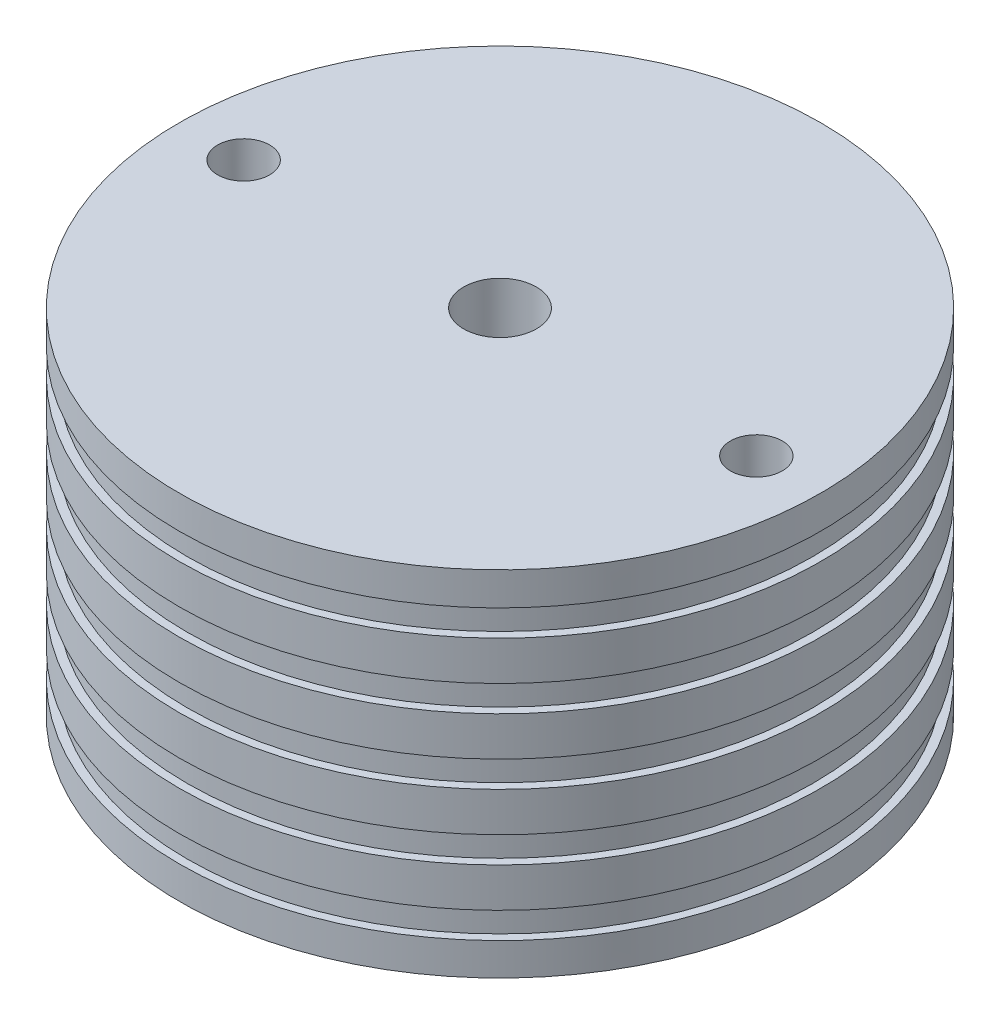
SolidWorks part; units mm, degrees
ref_plane "Front Plane" through (0, 0, 0) normal (0, 0, 1) x (1, 0, 0)
ref_plane "Top Plane" through (0, 0, 0) normal (0, 1, 0) x (1, 0, 0)
ref_plane "Right Plane" through (0, 0, 0) normal (1, 0, 0) x (0, 0, -1)
sketch "Sketch1" plane through (0, 0, 0) normal (0, 0, 1) x (1, 0, 0)
  line L0 (-5.5563, 0) -> (-49, 0)
  line L1 (-49, 0) -> (-49, -54)
  line L2 (-49, -54) -> (-45, -54)
  line L3 (-45, -54) -> (-45, -4)
  line L4 (-45, -4) -> (-10.5563, -4)
  line L5 (-10.5563, -4) -> (-10.5562, -20)
  line L6 (-10.5562, -20) -> (-5.5563, -20)
  line L7 (-5.5563, -20) -> (-5.5563, 0)
  line L8 (-5.5563, 0) -> (0, 0) construction
  line L10 (0, -56.2418) -> (0, 18.81) construction
  point P11 (-8.0562, -20)
  point P12 (0, -46.0845)
  point P14 (-5.5562, -10)
  dimension "D1" = 98
  dimension "D2" = 54
  dimension "D3" = 4
  dimension "D4" = 4
  dimension "D5" = 20
  dimension "D6" = 5
  dimension "D7" = 11.1125
revolve "Revolve1" add sketch "Sketch1" angle 360 about L10
sketch "Sketch2" plane through (0, 0, 0) normal (0, 0, 1) x (1, 0, 0)
  line L0 (0, 0) -> (-49, 0) construction
  line L1 (49, 0) -> (-49, 0) construction
  line L2 (-49, 0) -> (-49, -54) construction
  line L3 (-49, -54) -> (49, -54) construction
  line L4 (-49, -15.0408) -> (-49, -19.0408)
  line L5 (-49, -5.0408) -> (-47.75, -5.0408)
  line L6 (-49, -5.0408) -> (-49, -9.0408)
  line L7 (-49, -9.0408) -> (-47.75, -9.0408)
  line L8 (-47.75, -5.0408) -> (-47.75, -9.0408)
  line L9 (-49, -15.0408) -> (-47.75, -15.0408)
  line L10 (-47.75, -15.0408) -> (-47.75, -19.0408)
  line L11 (-49, -19.0408) -> (-47.75, -19.0408)
  line L12 (-49, -25.0408) -> (-49, -29.0408)
  line L13 (-49, -25.0408) -> (-47.75, -25.0408)
  line L14 (-47.75, -25.0408) -> (-47.75, -29.0408)
  line L15 (-49, -29.0408) -> (-47.75, -29.0408)
  line L16 (-49, -35.0408) -> (-49, -39.0408)
  line L17 (-49, -35.0408) -> (-47.75, -35.0408)
  line L18 (-47.75, -35.0408) -> (-47.75, -39.0408)
  line L19 (-49, -39.0408) -> (-47.75, -39.0408)
  line L20 (-49, -45.0408) -> (-49, -49.0408)
  line L21 (-49, -45.0408) -> (-47.75, -45.0408)
  line L22 (-47.75, -45.0408) -> (-47.75, -49.0408)
  line L23 (-49, -49.0408) -> (-47.75, -49.0408)
  line L24 (0, 0) -> (0, -19.7158) construction
  dimension "D1" = 49
  dimension "D2" = 54
  dimension "D3" = 4
  dimension "D4" = 1.25
  dimension "D5" = 5.0408
  dimension "D6" = 5
revolve "Cut-Revolve1" cut sketch "Sketch2" angle 360 about L24
sketch "Sketch3" plane through (0, -4, 0) normal (0, -1, 0) x (1, 0, 0)
  line L0 (-5.5563, 0) -> (-45, 0)
  line L1 (-2.7781, 4.8119) -> (-22.5, 38.9711)
  line L2 (2.7781, 4.8119) -> (22.5, 38.9711)
  line L3 (5.5563, 0) -> (45, 0)
  line L4 (2.7781, -4.8119) -> (22.5, -38.9711)
  line L5 (-2.7781, -4.8119) -> (-22.5, -38.9711)
  circle A0 centre (0, 0) radius 5.5563 construction
  circle A1 centre (0, 0) radius 45 construction
  circle A2 centre (0, 0) radius 10.5563 construction
  point P18 (0, 0)
  point P23 (0, 0)
  dimension "D2" = 2.7781
  dimension "D1" = 6
extrude "Extrude-Thin1" add sketch "Sketch3" along normal blind 48 thin thin type mid plane wall 4
sketch "Sketch4" plane through (0, 0, 0) normal (0, 0, 1) x (1, 0, 0)
  line L0 (0, 0) -> (-5.5563, 0) construction
  line L1 (0, 0) -> (0, -63.8052) construction
  line L3 (49, 0) -> (-49, 0) construction
  line L4 (5.5563, 0) -> (-5.5563, 0) construction
  line L7 (-5.5563, 0) -> (-10.5563, 0) construction
  line L11 (-10.5563, 0) -> (-10.5563, -5.0408) construction
  line L13 (-49, -5.0408) -> (49, -5.0408) construction
  line L15 (-10.5563, -5.0408) -> (-5.4843, -5.0408) construction
  line L17 (-10.5563, -5.0408) -> (-10.5563, -20)
  line L18 (-10.5563, -20) -> (-5.4843, -20)
  line L24 (-5.4843, -20) -> (-5.5563, -53)
  line L27 (-5.5563, -53) -> (-43.9289, -53)
  arc A0 (-43.9289, -53) -> (-23.1499, -16.1311) centre (6.2684, -57.0009) cw
  arc A2 (-10.5563, -20) -> (-23.1499, -16.1311) centre (-18.0483, -21.9562) ccw
  point P2 (-23.1499, -16.1311)
  dimension "D3" = 50.3565
  dimension "D4" = 7.7432
  dimension "D1" = 5.5563
  dimension "D2" = 5
  dimension "D5" = 6.2684
  dimension "D6" = 18.0483
  dimension "D7" = 5.4843
  dimension "D8" = 23.1499
  dimension "D9" = 43.9289
  dimension "D10" = 16.1311
revolve "Cut-Revolve3" cut sketch "Sketch4" angle 360 about L1 region at (-22.1021, -36.5991, 0)
sketch "Sketch5" plane through (0, -4, 0) normal (0, -1, 0) x (1, 0, 0)
  line L0 (0, 0) -> (0, 19.8661) construction
  line L1 (0, 0) -> (-39.154, 0) construction
  circle A0 centre (-39.154, 0) radius 6.7687
  circle A1 centre (-39.154, 0) radius 3.9687
  circle A2 centre (39.154, 0) radius 3.9687
  circle A3 centre (39.154, 0) radius 6.7687
  dimension "D1" = 2.8
  dimension "D2" = 7.9375
  dimension "D3" = 78.308
extrude "Boss-Extrude1" add sketch "Sketch5" along normal blind 30
extrude "Cut-Extrude1" cut sketch "Sketch5<3>" along normal through all both and the other way through all contours A1 | A1 | A2 region at (-39.154, -4, 0) region at (39.154, -4, 0)
sketch "Sketch5<3>" plane through (0, -4, 0) normal (0, -1, 0) x (1, 0, 0) same geometry as "Sketch5"
fillet "Fillet1" radius 5 28 edges at (-38.5501, -4, -23.2141) (-38.2417, -4, -6.707) (38.5501, -4, -23.2141) (38.2417, -4, -6.707) (38.5501, -4, 23.2141) (38.2417, -4, 6.707) (-38.2417, -4, 6.707) (-38.5501, -4, 23.2141) (-21.5263, -4, -2) (-9.142, -4, -5.2781) (-15.5622, -4, -22.9545) (15.5622, -4, -22.9545) (9.142, -4, -5.2781) (21.5263, -4, -2) (21.5263, -4, 2) (9.142, -4, 5.2781) (15.5622, -4, 22.9545) (-15.5622, -4, 22.9545) (-9.142, -4, 5.2781) (-21.5263, -4, 2) (12.0981, -4, -24.9545) (0, -4, -45) (-12.0981, -4, -24.9545) (0, -4, -10.5563) (-12.0981, -4, 24.9545) (0, -4, 45) (12.0981, -4, 24.9545) (0, -4, 10.5563)
